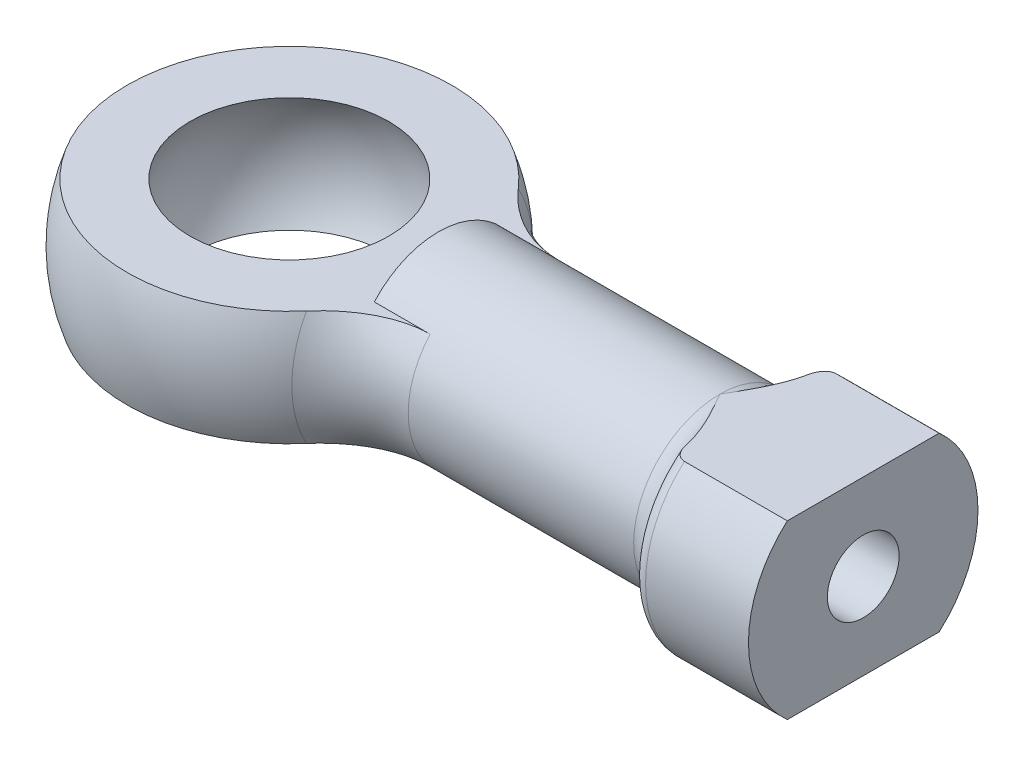
SolidWorks part; units mm, degrees
ref_plane "前视基准面" through (0, 0, 0) normal (0, 0, 1) x (1, 0, 0)
ref_plane "上视基准面" through (0, 0, 0) normal (0, 1, 0) x (1, 0, 0)
ref_plane "右视基准面" through (0, 0, 0) normal (1, 0, 0) x (0, 0, -1)
sketch "草图1" plane through (0, 0, 0) normal (0, 0, 1) x (1, 0, 0)
  line L0 (0, 6) -> (0, -6)
  arc A0 (0, -6) -> (0, 6) centre (0, 0) ccw
  dimension "D1" = 12
revolve "旋转1" add sketch "草图1" angle 360 about L0
sketch "草图2" plane through (0, 0, 0) normal (1, 0, 0) x (0, 0, -1)
  circle A0 centre (0, 0) radius 3
  dimension "D1" = 6
extrude "凸台-拉伸1" add sketch "草图2" along normal blind 16
sketch "草图3" plane through (0, 0, 0) normal (0, 0, 1) x (1, 0, 0)
  line L0 (16, -3) -> (16, 3) construction
  line L1 (16, 6) -> (16, -6)
  arc A0 (16, -6) -> (16, 6) centre (16, 0) ccw
  dimension "D1" = 6
revolve "旋转2" [suppressed] add sketch "草图3" angle 360 about L1
sketch "草图4" plane through (0, 0, 0) normal (0, 0, 1) x (1, 0, 0)
  line L0 (0, 13.8976) -> (0, -14.6344) construction
  line L1 (-12.5542, 0) -> (10.0025, 0) construction
  line L2 (0, 6) -> (0, -6)
  line L3 (-5.6569, 2) -> (-3.4641, 2)
  line L4 (-5.6569, -2) -> (-3.4641, -2)
  arc A0 (5.1962, 3) -> (5.1962, -3) centre (0, 0) ccw construction
  arc A1 (5.1962, 3) -> (5.1962, -3) centre (0, 0) ccw construction
  arc A2 (0, 6) -> (-5.6569, 2) centre (0, 0) ccw
  arc A3 (-3.4641, 2) -> (-3.4641, -2) centre (0, 0) ccw
  arc A4 (-5.6569, -2) -> (0, -6) centre (0, 0) ccw
  dimension "D1" = 4
  dimension "D2" = 6
  dimension "D3" = 4
revolve "切除-旋转1" cut sketch "草图4" angle 360 about L0
sketch "草图5" [suppressed] plane through (0, 0, 0) normal (0, 0, 1) x (1, 0, 0)
  line L0 (83.1, 11.1703) -> (83.1, -10.7078) construction
  line L1 (83.1, 0) -> (111.9433, 0) construction
  line L2 (88.7569, 2) -> (86.5641, 2)
  line L3 (88.7569, -2) -> (86.5641, -2)
  line L4 (83.1, 6) -> (83.1, -6)
  arc A0 (77.4431, -2) -> (77.4431, 2) centre (83.1, 0) ccw construction
  arc A1 (77.4431, -2) -> (77.4431, 2) centre (83.1, 0) ccw construction
  arc A2 (86.5641, -2) -> (86.5641, 2) centre (83.1, 0) ccw
  arc A3 (88.7569, 2) -> (83.1, 6) centre (83.1, 0) ccw
  arc A4 (83.1, -6) -> (88.7569, -2) centre (83.1, 0) ccw
  dimension "D1" = 4
  dimension "D2" = 6
  dimension "D3" = 4
revolve "切除-旋转2" [suppressed] cut sketch "草图5" angle 360 about L0
sketch "草图6" plane through (16, 0, 0) normal (1, 0, 0) x (0, 0, -1)
  circle A0 centre (0, 0) radius 4
  dimension "D1" = 8
extrude "凸台-拉伸2" add sketch "草图6" along normal blind 4
fillet "圆角1" radius 1 1 edges at (16, 0, -3)
fillet "圆角2" radius 0.5 1 edges at (16, 0, -4)
sketch "草图7" plane through (20, 0, 0) normal (1, 0, 0) x (0, 0, -1)
  line L1 (-2.6458, 3) -> (2.6458, 3)
  line L2 (0, 0) -> (4.1391, 0) construction
  line L3 (-2.6458, -3) -> (2.6458, -3)
  arc A0 (-2.6458, -3) -> (2.6458, -3) centre (0, 0) ccw
  arc A1 (2.6458, 3) -> (-2.6458, 3) centre (0, 0) ccw
  dimension "D2" = 4
  dimension "D1" = 6
extrude "切除-拉伸1" cut sketch "草图7" against normal through all
fillet "圆角3" radius 4 2 edges at (5.1962, 0, -3) (5.1962, 0, 3)
sketch "草图8" plane through (20, 0, 0) normal (1, 0, 0) x (0, 0, -1)
  circle A0 centre (0, 0) radius 1.25
  dimension "D1" = 2.5
extrude "切除-拉伸2" cut sketch "草图8" against normal blind 8
cosmetic thread "装饰螺纹线1" parameters "D1"=8, "D2"=3
